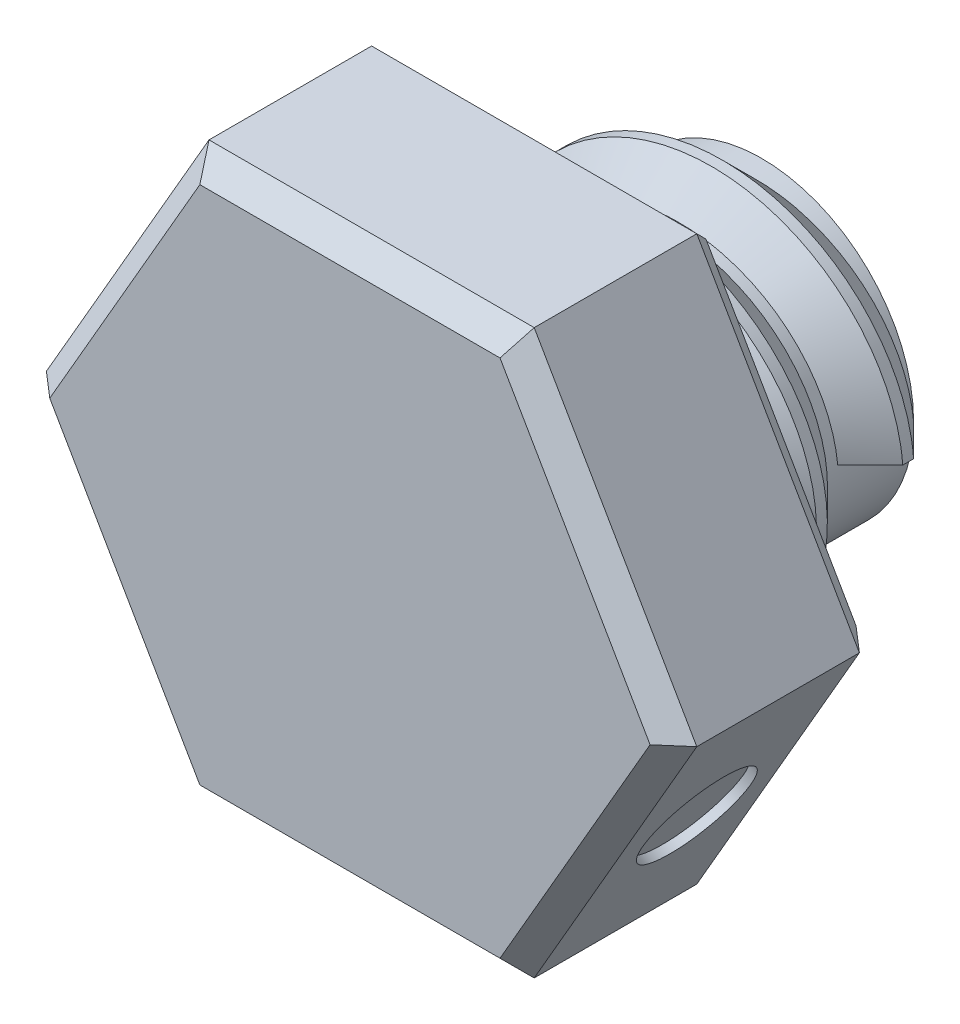
SolidWorks part; units mm, degrees
ref_plane "前视基准面" through (0, 0, 0) normal (0, 0, 1) x (1, 0, 0)
ref_plane "上视基准面" through (0, 0, 0) normal (0, 1, 0) x (1, 0, 0)
ref_plane "右视基准面" through (0, 0, 0) normal (1, 0, 0) x (0, 0, -1)
sketch "草图1" plane through (0, 0, 0) normal (0, 0, 1) x (1, 0, 0)
  line L1 (15, 0) -> (7.5, 12.9904)
  line L2 (7.5, 12.9904) -> (-7.5, 12.9904)
  line L3 (-7.5, 12.9904) -> (-15, 0)
  line L4 (-15, 0) -> (-7.5, -12.9904)
  line L5 (-7.5, -12.9904) -> (7.5, -12.9904)
  line L6 (7.5, -12.9904) -> (15, 0)
  circle A0 centre (0, 0) radius 15
  circle A1 centre (0, 0) radius 12.9904 construction
  dimension "D1" = 30
extrude "凸台-拉伸1" add sketch "草图1" along normal blind 9.5 contours L2 L3 L4 L5 L6 L1
sketch "草图2" plane through (0, 0, 0) normal (0, 0, -1) x (-1, 0, 0)
  circle A0 centre (0, 0) radius 7
  circle A1 centre (0, 0) radius 9
  dimension "D1" = 14
  dimension "D2" = 2
sketch "草图6" plane through (0, 0, 0) normal (0, 0, -1) x (-1, 0, 0)
  circle A0 centre (0, 0) radius 7 construction
  circle A1 centre (0, 0) radius 7
extrude "凸台-拉伸2" add sketch "草图6" along normal blind 9.5
sketch "草图5" plane through (0, 0, 0) normal (0, 0, -1) x (-1, 0, 0)
  circle A0 centre (0, 0) radius 7 construction
  circle A1 centre (0, 0) radius 7
ref_plane "基准面1" through (0, 0, -1.75) normal (0, 0, -1) x (-1, 0, 0)
sketch "草图7" plane through (0, 0, -1.75) normal (0, 0, -1) x (-1, 0, 0)
  circle A0 centre (0, 0) radius 7 construction
  circle A1 centre (0, 0) radius 7
curve "螺旋线/涡状线2" pitch 4 height 6 radius 7 centre (0, 0, -1.75) axis (0, 0, -1) start towards (-1, 0, 0)
sketch "草图8" plane through (0, 0, 0) normal (0, 1, 0) x (1, 0, 0)
  line L0 (-7, 3.5) -> (-7, 0)
  line L1 (-7, 0) -> (-8.5, 1.5)
  line L2 (-8.5, 1.5) -> (-8.5, 2)
  line L3 (-8.5, 2) -> (-7, 3.5)
  point P7 (-7, 1.75)
  dimension "D1" = 1.5
  dimension "D2" = 3.5
  dimension "D3" = 45
  dimension "D4" = 45
sweep "扫描1" add profiles "草图8" path "螺旋线/涡状线2"
sketch "草图9" plane through (0, 0, 0) normal (0, 1, 0) x (1, 0, 0)
  line L0 (9, 0) -> (-9, 0) construction
  line L1 (0, 0) -> (0, 50000) construction
  line L2 (7, 0) -> (7, 2) construction
  line L3 (7, 3.5) -> (7, 0)
  line L4 (7, 3.5) -> (8.5, 2)
  line L5 (8.5, 2) -> (8.5, 1.5)
  line L6 (8.5, 1.5) -> (7, 0)
  point P8 (11.4749, 6.2988)
  dimension "D1" = 3.5
  dimension "D2" = 45
  dimension "D3" = 45
  dimension "D4" = 1.5
revolve "旋转2" add sketch "草图9" angle 45 about L1 reverse direction yes
chamfer "倒角1" distance 1 angle 45 12 edges at (0, -12.9904, 0) (11.25, -6.4952, 0) (-11.25, -6.4952, 0) (-11.25, 6.4952, 0) (0, 12.9904, 0) (11.25, 6.4952, 0) (-11.25, 6.4952, 9.5) (-11.25, -6.4952, 9.5) (0, -12.9904, 9.5) (11.25, -6.4952, 9.5) (11.25, 6.4952, 9.5) (0, 12.9904, 9.5)
sketch "草图11" plane through (-11.25, -6.4952, 0) normal (-0.866, -0.5, 0) x (0, 0, 1)
  line L0 (1, 0) -> (8.5, 0) construction
  line L8 (1, 7.5) -> (1, -7.5) construction
  line L9 (8.5, -7.5) -> (8.5, 7.5) construction
  line L10 (2.25, 0) -> (7.25, 2.8868)
  line L11 (7.25, 2.8868) -> (7.25, -2.8868)
  line L12 (7.25, -2.8868) -> (2.25, 0)
  line L13 (2.25, 0) -> (7.25, 0) construction
  line L14 (4.75, 0) -> (4.75, -1.2379) construction
  point P12 (4.75, 0)
  dimension "D1" = 5
extrude "切除-拉伸2" cut sketch "草图11" against normal blind 0.4
sketch "草图12" plane through (0, -12.9904, 0) normal (0, -1, 0) x (1, 0, 0)
  line L0 (0, 8.5) -> (0, 1) construction
  line L1 (7.5, 8.5) -> (-7.5, 8.5) construction
  line L2 (-7.5, 1) -> (7.5, 1) construction
  line L3 (-2.5, 7.25) -> (2.5, 2.25) construction
  line L4 (2.5, 2.25) -> (-2.5, 2.25)
  line L5 (2.5, 2.25) -> (2.5, 7.25)
  line L6 (2.5, 7.25) -> (-2.5, 7.25)
  line L7 (-2.5, 2.25) -> (-2.5, 7.25)
  line L8 (0, 7.25) -> (0, 2.25) construction
  line L9 (2.5, 4.75) -> (-2.5, 4.75) construction
  line L10 (2.5, 7.25) -> (-2.5, 2.25) construction
  line L11 (-2.5, 6.8257) -> (2.0757, 2.25)
  line L12 (-2.0757, 7.25) -> (2.5, 2.6743)
  line L13 (2.0757, 7.25) -> (-2.5, 2.6743)
  line L14 (2.5, 6.8257) -> (-2.0757, 2.25)
  line L15 (-2.7121, 7.0379) -> (2.2879, 2.0379) construction
  line L16 (-2.2879, 7.4621) -> (2.7121, 2.4621) construction
  line L17 (2.2879, 7.4621) -> (-2.7121, 2.4621) construction
  line L18 (2.7121, 7.0379) -> (-2.2879, 2.0379) construction
  line L19 (-2.5, 6.8257) -> (-2.0757, 7.25)
  line L20 (2.0757, 7.25) -> (2.5, 6.8257)
  line L21 (-2.5, 2.6743) -> (-2.0757, 2.25)
  line L22 (2.0757, 2.25) -> (2.5, 2.6743)
  point P6 (0, 4.75)
  dimension "D1" = 5
  dimension "D2" = 0.3
  dimension "D3" = 0.3
  dimension "D4" = 0.3
  dimension "D5" = 0.3
sketch "草图13" plane through (11.25, -6.4952, 0) normal (0.866, -0.5, 0) x (0, 0, -1)
  line L0 (-8.5, 0) -> (-1, 0) construction
  line L1 (-8.5, 7.5) -> (-8.5, -7.5) construction
  line L2 (-1, -7.5) -> (-1, 7.5) construction
  circle A0 centre (-4.75, 0) radius 2.5
  dimension "D1" = 5
sketch "草图14" plane through (-11.25, 6.4952, 0) normal (-0.866, 0.5, 0) x (0, 0, 1)
  line L0 (1, 0) -> (8.5, 0) construction
  line L1 (1, 7.5) -> (1, -7.5) construction
  line L2 (8.5, -7.5) -> (8.5, 7.5) construction
  line L4 (7.25, -2.5) -> (2.25, -2.5)
  line L5 (7.25, -2.5) -> (7.25, 2.5)
  line L6 (7.25, 2.5) -> (2.25, 2.5)
  line L7 (2.25, -2.5) -> (2.25, 2.5)
  line L8 (4.75, 2.5) -> (4.75, -2.5) construction
  line L9 (7.25, 0) -> (2.25, 0) construction
  point P6 (4.75, 0)
  dimension "D1" = 5
extrude "切除-拉伸3" cut sketch "草图13" against normal blind 0.4 contours A0
extrude "切除-拉伸4" cut sketch "草图12" against normal blind 0.4 contours L13 L21 L14 L11 | L20 L13 L12 L14 | L11 L22 L12 L19 region at (-1.25, -12.9904, 3.5) region at (1.25, -12.9904, 6)
extrude "切除-拉伸5" cut sketch "草图14" against normal blind 0.4 contours L6 L7 L4 L5
